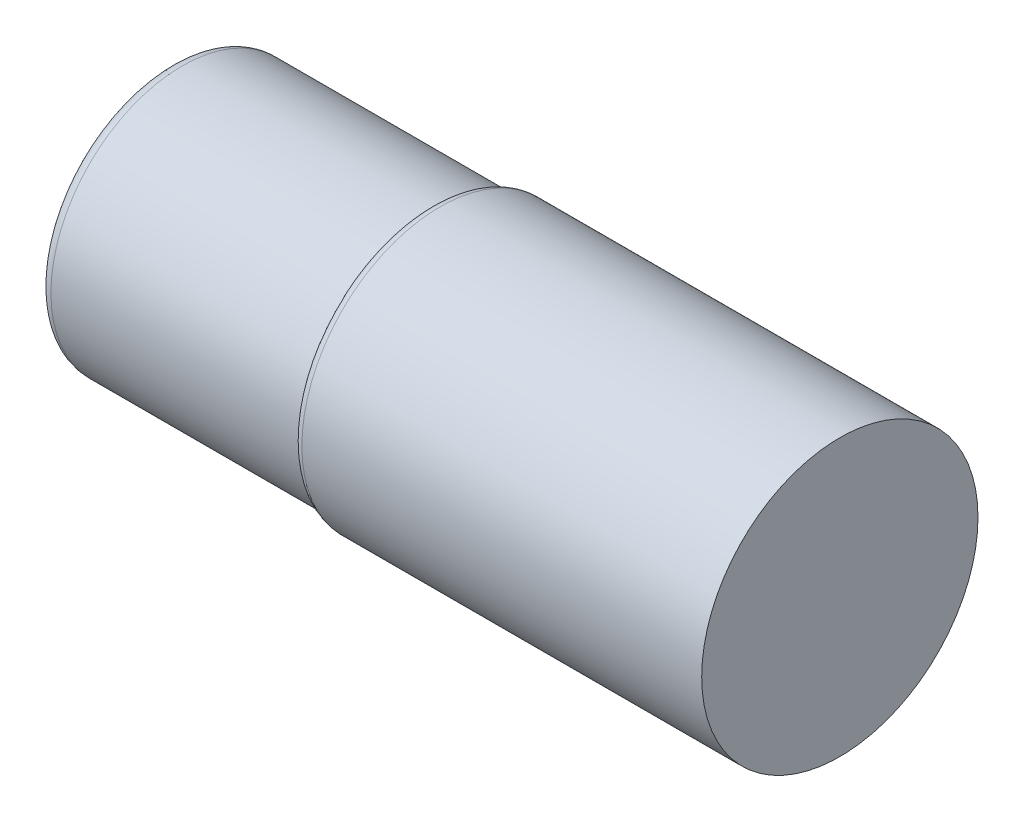
SolidWorks part; units mm, degrees
ref_plane "Front Plane" through (0, 0, 0) normal (0, 0, 1) x (1, 0, 0)
ref_plane "Top Plane" through (0, 0, 0) normal (0, 1, 0) x (1, 0, 0)
ref_plane "Right Plane" through (0, 0, 0) normal (1, 0, 0) x (0, 0, -1)
sketch "Sketch1" plane through (0, 0, 0) normal (0, 0, 1) x (1, 0, 0)
  line L0 (0, 0) -> (0, 21)
  line L1 (0, 21) -> (43.7, 21)
  line L2 (0, 0) -> (110.2, 0)
  line L4 (43.7, 21) -> (43.7, 21.65)
  line L5 (44.2, 22.15) -> (45.2, 22.15)
  line L10 (110.2, 0) -> (110.2, 22.15)
  line L11 (110.2, 22.15) -> (45.2, 22.15)
  arc A0 (44.2, 22.15) -> (43.7, 21.65) centre (44.2, 21.65) ccw
  point P9 (110.2, 11.075)
  point P16 (43.7, -0.85)
  dimension "D5" = 0.5
  dimension "D2" = 21
  dimension "D3" = 22.15
  dimension "D4" = 110.2
revolve "Revolve1" add sketch "Sketch1" angle 360 about L2
sketch "Sketch2" plane through (0, 0, 0) normal (-1, 0, 0) x (0, 0, 1)
  line L0 (0, 21) -> (0, -21) construction
  line L1 (-21, 0) -> (21, 0) construction
  line L2 (0, 0) -> (-14.8492, 14.8492) construction
  circle A0 centre (0, 0) radius 17.5 construction
  circle A1 centre (0, 0) radius 21 construction
  circle A2 centre (0, 0) radius 21 construction
  circle A3 centre (-12.3744, 12.3744) radius 2
  circle A4 centre (12.3744, 12.3744) radius 2
  circle A5 centre (12.3744, -12.3744) radius 2
  circle A6 centre (-12.3744, -12.3744) radius 2
  dimension "D1" = 35
  dimension "D2" = 4
  dimension "D3" = 4
extrude "Cut-Extrude1" cut sketch "Sketch2" against normal blind 10
sketch "Sketch3" plane through (0, 0, 0) normal (-1, 0, 0) x (0, 0, 1)
  circle A0 centre (0, 0) radius 13
  dimension "D1" = 26
extrude "Boss-Extrude2" add sketch "Sketch3" along normal blind 2
fillet "Fillet1" radius 1 1 edges at (0, 0, 21)
fillet "Fillet2" radius 1 1 edges at (-2, 0, 13)
sketch "Sketch4" plane through (-2, 0, 0) normal (-1, 0, 0) x (0, 0, 1)
  circle A0 centre (0, 0) radius 11
  dimension "D1" = 22
extrude "Cut-Extrude2" cut sketch "Sketch4" against normal blind 10
shell "Shell4" thickness 1 removed face at (8, 0, 11) outward yes
